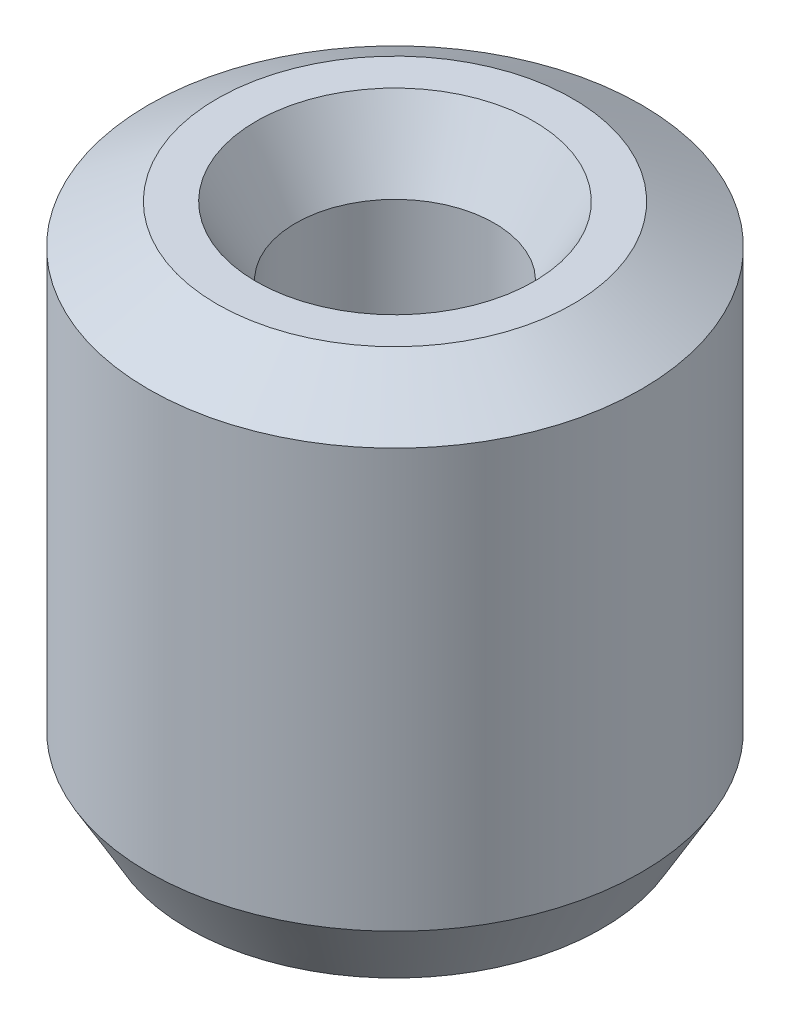
SolidWorks part; units mm, degrees
ref_plane "Front Plane" through (0, 0, 0) normal (0, 0, 1) x (1, 0, 0)
ref_plane "Top Plane" through (0, 0, 0) normal (0, 1, 0) x (1, 0, 0)
ref_plane "Right Plane" through (0, 0, 0) normal (1, 0, 0) x (0, 0, -1)
sketch "Sketch1" plane through (0, 0, 0) normal (0, 1, 0) x (1, 0, 0)
  circle A0 centre (0, 0) radius 17.5
  dimension "SLEEVE_OD" = 35
extrude "Boss-Extrude1" add sketch "Sketch1" along normal blind 37.3806
sketch "Sketch2" plane through (0, 0, 0) normal (0, 1, 0) x (1, 0, 0)
  circle A0 centre (0, 0) radius 7.0564
  dimension "BORE_D" = 14.1128
extrude "Cut-Extrude1" cut sketch "Sketch2" along normal through all
chamfer "Chamfer1" distance 2.8065 angle 60 4 edges at (0, 37.3806, 7.0564) (0, 0, 7.0564) (0, 0, 17.5) (0, 37.3806, 17.5) first distance on face at (0, 37.3806, 7.0564) first distance on face at (0, 0, 7.0564) first distance on face at (0, 37.3806, 17.5)
